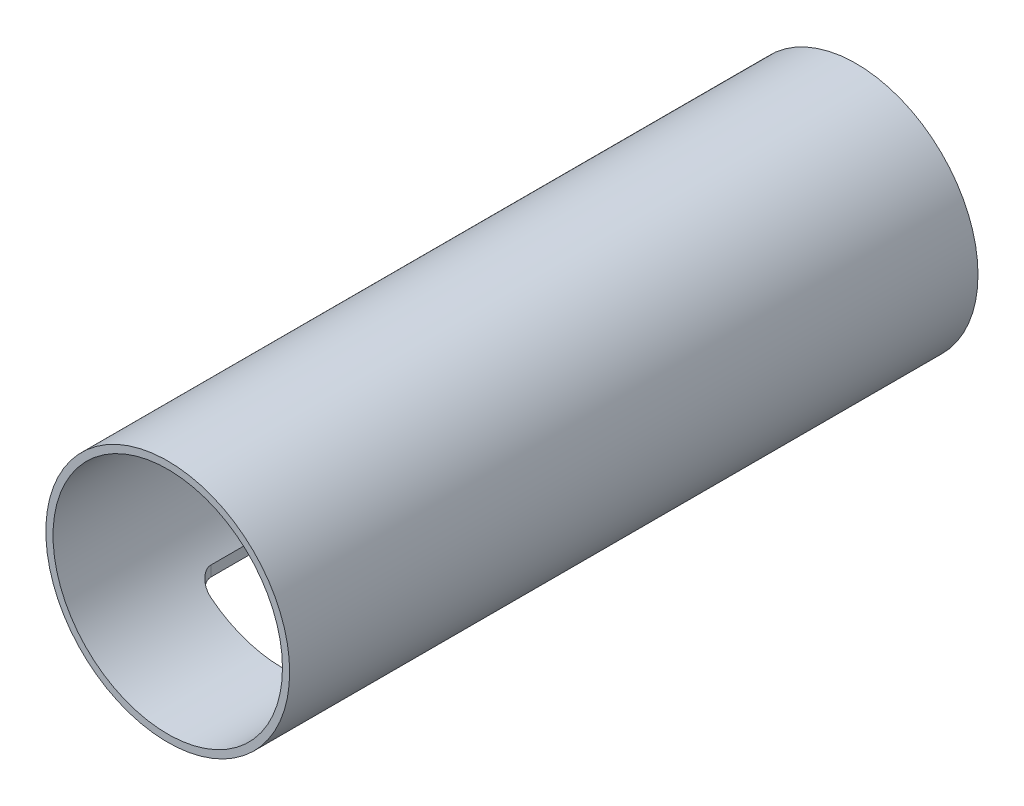
SolidWorks part; units mm, degrees
ref_plane "Front Plane" through (0, 0, 0) normal (0, 0, 1) x (1, 0, 0)
ref_plane "Top Plane" through (0, 0, 0) normal (0, 1, 0) x (1, 0, 0)
ref_plane "Right Plane" through (0, 0, 0) normal (1, 0, 0) x (0, 0, -1)
sketch "Sketch1" plane through (0, 0, 0) normal (0, 0, 1) x (1, 0, 0)
  circle A0 centre (0, 0) radius 50.8
  circle A1 centre (0, 0) radius 53.975
  dimension "D1" = 101.6
  dimension "D2" = 3.175
extrude "Extrude1" add sketch "Sketch1" along normal blind 304.8
sketch "Sketch2" plane through (0, 0, 0) normal (0, 1, 0) x (1, 0, 0)
  line L0 (0, 0) -> (0, -304.8) construction
  line L1 (-38.1, -50.8) -> (38.1, -50.8)
  line L2 (-38.1, -50.8) -> (-38.1, -254)
  line L3 (-38.1, -254) -> (38.1, -254)
  line L4 (38.1, -50.8) -> (38.1, -254)
  line L5 (-53.975, -304.8) -> (53.975, -304.8) construction
  point P4 (0, -50.8)
  point P9 (38.1, -152.4)
  point P13 (0, -152.4)
  dimension "D1" = 76.2
  dimension "D2" = 203.2
extrude "Extrude2" cut sketch "Sketch2" against normal through all
fillet "Fillet1" radius 6.35 4 edges at (38.1, -35.9166, 254) (-38.1, -35.9166, 254) (38.1, -35.9166, 50.8) (-38.1, -35.9166, 50.8)
